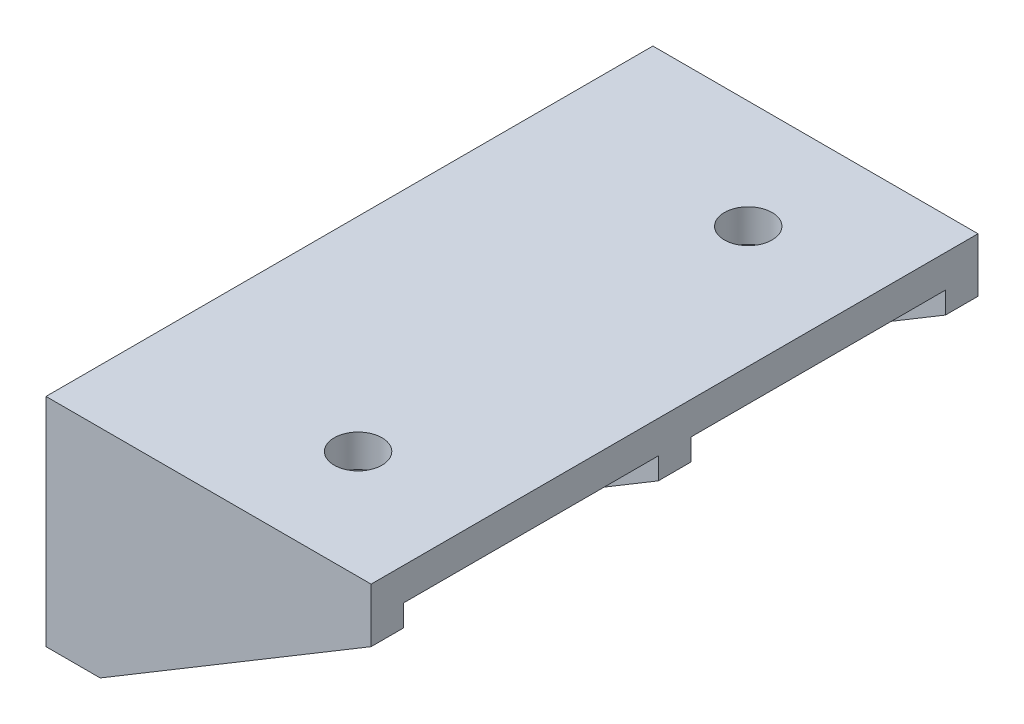
SolidWorks part; units mm, degrees
ref_plane "前视基准面" through (0, 0, 0) normal (0, 0, 1) x (1, 0, 0)
ref_plane "上视基准面" through (0, 0, 0) normal (0, 1, 0) x (1, 0, 0)
ref_plane "右视基准面" through (0, 0, 0) normal (1, 0, 0) x (0, 0, -1)
other "Configuration Table"
sketch "草图1" plane through (0, 0, 0) normal (0, 0, 1) x (1, 0, 0)
  line L1 (0, 0) -> (0, 20)
  line L2 (0, 20) -> (30, 20)
  line L7 (30, 17) -> (30, 20)
  line L8 (0, 0) -> (3, 0)
  line L9 (30, 17) -> (3, 17)
  line L10 (3, 17) -> (3, 0)
  point P0 (30, 21.5269)
  dimension "D1" = 3
  dimension "D2" = 30
  dimension "D3" = 3
  dimension "D5" = 20
extrude "凸台-拉伸1" add sketch "草图1" along normal mid plane 56
sketch "草图2" plane through (0, 0, 0) normal (0, 0, 1) x (1, 0, 0)
  line L0 (3, 0) -> (5, 0)
  line L1 (5, 0) -> (30, 15)
  line L2 (30, 15) -> (30, 17)
  line L3 (30, 17) -> (3, 17)
  line L4 (3, 17) -> (3, 0)
  dimension "D1" = 2
  dimension "D2" = 2
extrude "凸台-拉伸2" add sketch "草图2" against normal blind 3 from surface starting at face at (11, 12.3333, 28)
extrude "凸台-拉伸3" add sketch "草图2<2>" along normal mid plane 3
sketch "草图2<2>" plane through (0, 0, 0) normal (0, 0, 1) x (1, 0, 0) same geometry as "草图2"
extrude "凸台-拉伸4" add sketch "草图2<3>" along normal blind 3 from surface starting at face at (11, 12.3333, -28)
sketch "草图2<3>" plane through (0, 0, 0) normal (0, 0, 1) x (1, 0, 0) same geometry as "草图2"
sketch "草图3" plane through (0, 0, 0) normal (0, 1, 0) x (1, 0, 0)
  line L0 (-10.6562, 0) -> (36.1472, 0) construction
  line L1 (30, -28) -> (30, 28) construction
  circle A0 centre (18.8, 18) radius 2.2
  circle A1 centre (18.8, -18) radius 2.2
  dimension "D1" = 4.4
  dimension "D2" = 36
  dimension "D3" = 11.2
extrude "切除-拉伸1" cut sketch "草图3" along normal up to next
sketch "草图4" plane through (0, 0, 0) normal (1, 0, 0) x (0, 0, -1)
  line L0 (0, -8.9458) -> (0, 27.2678) construction
  circle A0 centre (-18, 10) radius 1.7
  circle A1 centre (18, 10) radius 1.7
  dimension "D2" = 3.4
  dimension "D1" = 36
  dimension "D3" = 10
extrude "切除-拉伸2" cut sketch "草图4" along normal up to next
